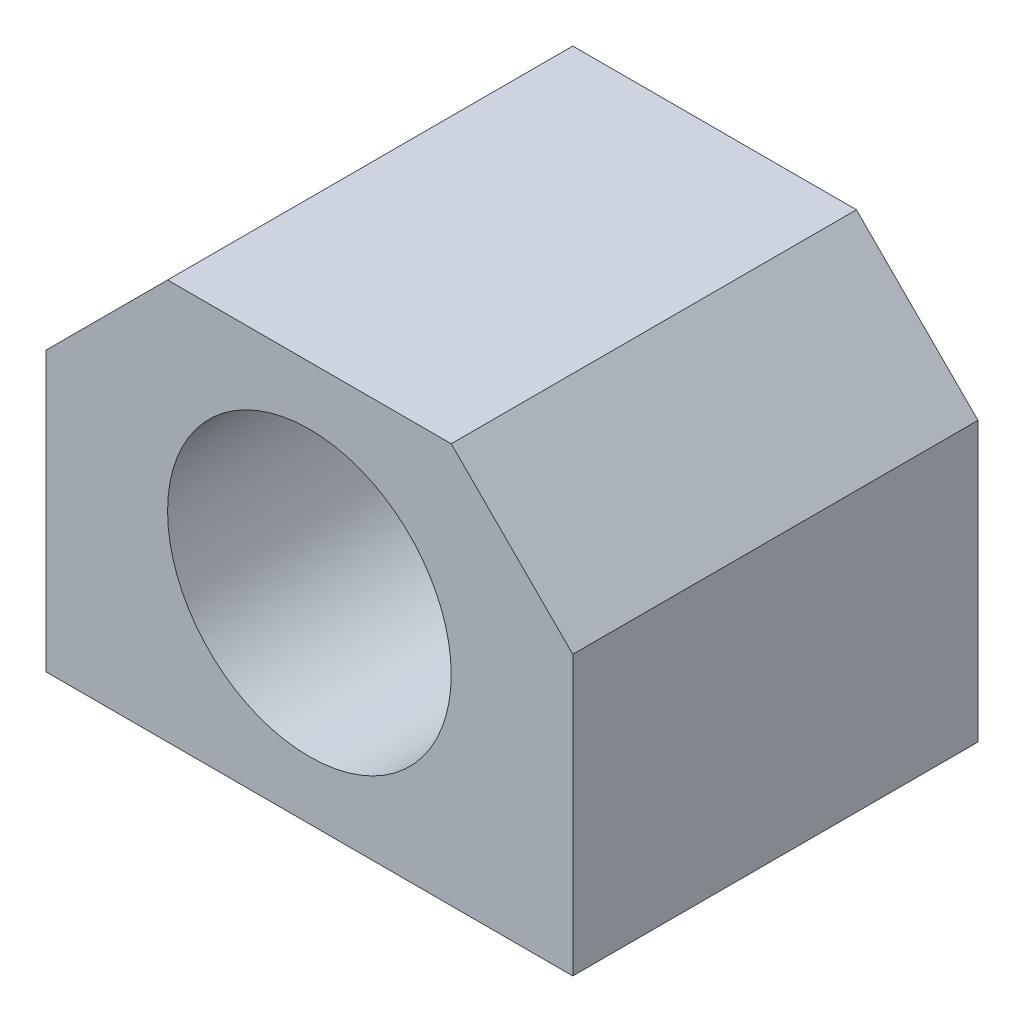
SolidWorks part; units mm, degrees
note: The reader was unsure of these and kept them because the rebuilt part matched: shared geometry of "Sketch1<3>".
ref_plane "Front Plane" through (0, 0, 0) normal (0, 0, 1) x (1, 0, 0)
ref_plane "Top Plane" through (0, 0, 0) normal (0, 1, 0) x (1, 0, 0)
ref_plane "Right Plane" through (0, 0, 0) normal (1, 0, 0) x (0, 0, -1)
sketch "Sketch1" plane through (0, 0, 0) normal (0, 0, 1) x (1, 0, 0)
  line L1 (-26, -19.75) -> (26, -19.75)
  line L2 (-26, -19.75) -> (-26, 19.75)
  line L3 (-26, 19.75) -> (26, 19.75)
  line L4 (26, -19.75) -> (26, 19.75)
  line L5 (-26, -19.75) -> (26, 19.75) construction
  line L6 (-26, 19.75) -> (26, -19.75) construction
  circle A0 centre (0, 0) radius 14
  circle A1 centre (0, 0) radius 18.75 construction
  circle A2 centre (18.75, 0) radius 2.5
  circle A3 centre (13.2583, -13.2583) radius 2.5
  circle A4 centre (0, -18.75) radius 2.5 [skipped]
  circle A5 centre (-13.2583, -13.2583) radius 2.5
  circle A6 centre (-18.75, 0) radius 2.5
  circle A7 centre (-13.2583, 13.2583) radius 2.5
  circle A8 centre (0, 18.75) radius 2.5 [skipped]
  circle A9 centre (13.2583, 13.2583) radius 2.5
  point P0 (0, 0)
  point P28 (0, 0)
  dimension "D3" = 28
  dimension "D4" = 37.5
  dimension "D5" = 5
  dimension "D1" = 52
  dimension "D2" = 39.5
  dimension "D6" = 8
extrude "Boss-Extrude1" add sketch "Sketch1" along normal blind 40 contours A9 | A7 | A2 | A6 | A5 | A3 | L1 L4 L3 L2 A9 A7 A6 A5 A3 A2 A0
chamfer "Chamfer1" distance 12 angle 45 2 edges at (-26, 19.75, 20) (26, 19.75, 20)
extrude "Cut-Extrude1" cut sketch "Sketch1<3>" along normal blind 16.5 contours A9 | A2 | A3 | A5 | A6 | A7
sketch "Sketch1<3>" plane through (0, 0, 0) normal (0, 0, 1) x (1, 0, 0) same geometry as "Sketch1"
sketch "Sketch2" plane through (0, -19.75, 0) normal (0, -1, 0) x (1, 0, 0)
  line L0 (0, 0) -> (0, 40) construction
  line L1 (-26, 0) -> (26, 0) construction
  line L2 (-26, 40) -> (26, 40) construction
  line L4 (20, 8) -> (-20, 8) construction
  line L5 (20, 8) -> (20, 32) construction
  line L6 (20, 32) -> (-20, 32) construction
  line L7 (-20, 8) -> (-20, 32) construction
  line L8 (20, 8) -> (-20, 32) construction
  line L9 (20, 32) -> (-20, 8) construction
  circle A0 centre (20, 8) radius 2.5
  circle A1 centre (-20, 8) radius 2.5
  circle A2 centre (20, 32) radius 2.5
  circle A3 centre (-20, 32) radius 2.5
  point P6 (0, 20)
  dimension "D1" = 40
  dimension "D2" = 24
extrude "Cut-Extrude2" cut sketch "Sketch2" against normal blind 8
